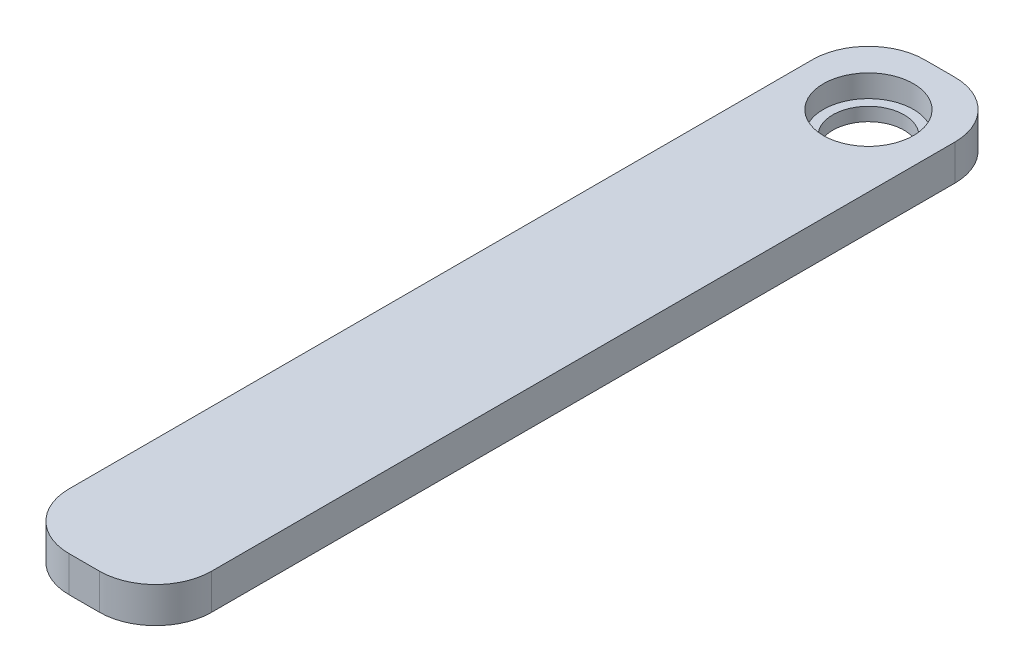
SolidWorks part; units mm, degrees
ref_plane "Front Plane" through (0, 0, 0) normal (0, 0, 1) x (1, 0, 0)
ref_plane "Top Plane" through (0, 0, 0) normal (0, 1, 0) x (1, 0, 0)
ref_plane "Right Plane" through (0, 0, 0) normal (1, 0, 0) x (0, 0, -1)
sketch "Sketch1" plane through (0, 0, 0) normal (0, 1, 0) x (1, 0, 0)
  line L1 (0, 0) -> (25.4, 0)
  line L2 (0, 0) -> (0, 152.4)
  line L3 (0, 152.4) -> (25.4, 152.4)
  line L4 (25.4, 0) -> (25.4, 152.4)
  dimension "D1" = 152.4
  dimension "D2" = 25.4
extrude "Boss-Extrude1" add sketch "Sketch1" along normal blind 6.35
sketch "Sketch5" plane through (0, 6.35, 0) normal (0, 1, 0) x (1, 0, 0)
  line L0 (0, 152.4) -> (0, 0) construction
  line L1 (25.4, 0) -> (25.4, 152.4) construction
  line L2 (25.4, 152.4) -> (0, 152.4) construction
  circle A0 centre (12.7, 139.7) radius 8.0169
  dimension "D3" = 16.0337
  dimension "D1" = 25.4
  dimension "D2" = 12.7
extrude "Cut-Extrude1" cut sketch "Sketch5" against normal blind 3.9688
sketch "Sketch6" plane through (0, 2.3812, 0) normal (0, 1, 0) x (1, 0, 0)
  circle A0 centre (12.7, 139.7) radius 6.35
  dimension "D1" = 12.7
extrude "Cut-Extrude2" cut sketch "Sketch6" against normal through all
sketch "Sketch7" plane through (0, 6.35, 0) normal (0, 1, 0) x (1, 0, 0)
  line L0 (25.4, 0) -> (25.4, 152.4) construction
  line L1 (0, 0) -> (25.4, 0) construction
  circle A0 centre (12.7, 6.35) radius 3.429
  dimension "D3" = 6.858
  dimension "D1" = 12.7
  dimension "D2" = 6.35
extrude "Cut-Extrude3" cut sketch "Sketch7" against normal blind 7.62
ref_axis "Axis1" through (12.7, 0, -6.35) along (0, 1, 0)
sketch "Sketch9" plane through (0, 6.35, 0) normal (0, 1, 0) x (1, 0, 0)
  line L1 (17.9251, 10.5572) -> (6.7267, 10.5572)
  line L2 (17.9251, 10.5572) -> (17.9251, 8.7376)
  line L3 (17.9251, 8.7376) -> (6.7267, 8.7376)
  line L4 (6.7267, 10.5572) -> (6.7267, 8.7376)
  dimension "D1" = 2.3876
extrude "Boss-Extrude2" add sketch "Sketch9" against normal through all
sketch "Sketch11" plane through (0, 0, 0) normal (0, -1, 0) x (1, 0, 0)
  line L1 (19.2592, -10.2867) -> (5.6226, -10.2867)
  line L2 (19.2592, -10.2867) -> (19.2592, -1.9718)
  line L3 (19.2592, -1.9718) -> (5.6226, -1.9718)
  line L4 (5.6226, -10.2867) -> (5.6226, -1.9718)
extrude "Boss-Extrude4" add sketch "Sketch11" along normal blind 1.27 from surface starting at face at (12.7, 6.35, -5.8293)
fillet "Fillet1" radius 10 4 edges at (0, 3.175, 0) (25.4, 3.175, 0) (25.4, 3.175, -152.4) (0, 3.175, -152.4)
